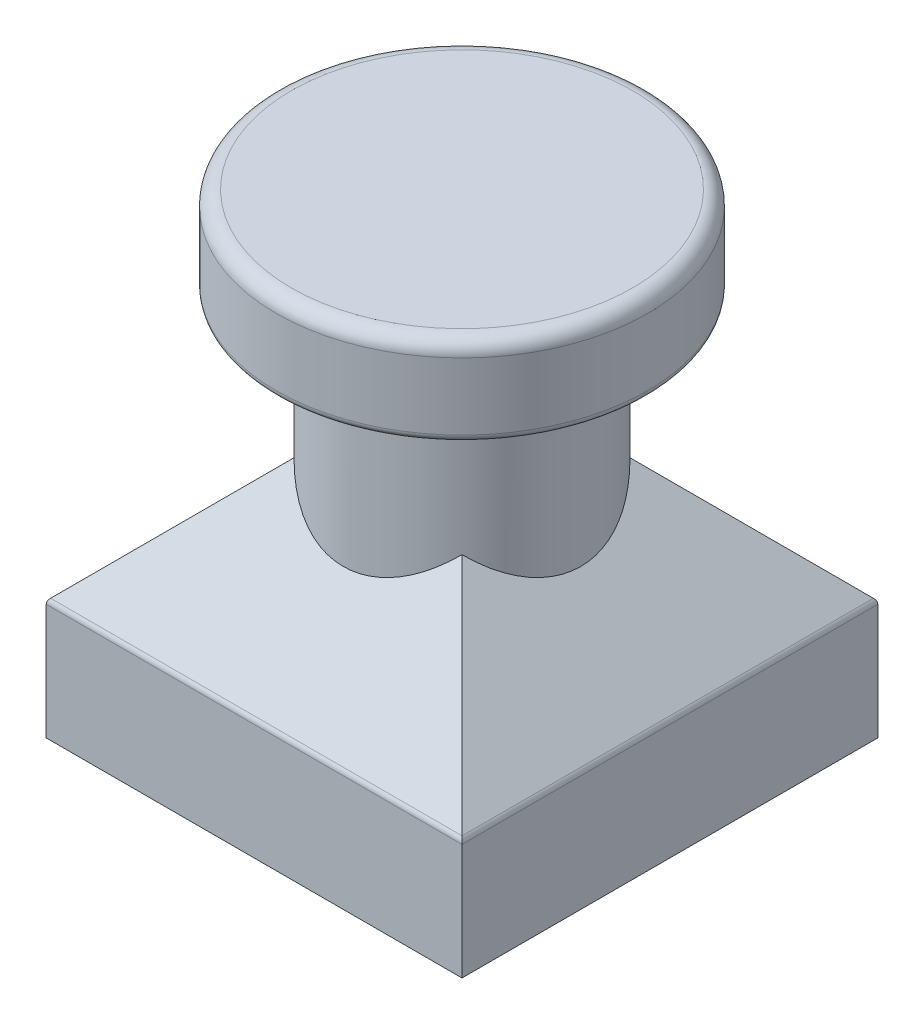
SolidWorks part; units mm, degrees
ref_plane "Ebene vorne" through (0, 0, 0) normal (0, 0, 1) x (1, 0, 0)
ref_plane "Ebene oben" through (0, 0, 0) normal (0, 1, 0) x (1, 0, 0)
ref_plane "Ebene rechts" through (0, 0, 0) normal (1, 0, 0) x (0, 0, -1)
sketch "Skizze1" plane through (0, 0, 0) normal (0, 1, 0) x (1, 0, 0)
  line L0 (-7, 0) -> (7, 0) construction
  line L1 (-7, 7) -> (7, 7)
  line L2 (-7, 7) -> (-7, -7)
  line L3 (-7, -7) -> (7, -7)
  line L4 (7, 7) -> (7, -7)
  line L5 (-7, 7) -> (7, -7) construction
  line L6 (-7, -7) -> (7, 7) construction
  line L7 (0, 7) -> (0, -7) construction
  point P0 (0, 0)
  dimension "D1" = 14
  dimension "D2" = 14
extrude "Aufsatz-Linear austragen1" add sketch "Skizze1" along normal blind 16
sketch "Skizze6" plane through (0, 0, 0) normal (1, 0, 0) x (0, 0, -1)
  line L0 (13.25, 16) -> (13.25, 9)
  line L2 (13.25, 9) -> (4, 9)
  line L3 (4, 9) -> (4, 13)
  line L4 (4, 13) -> (6.25, 13)
  line L5 (6.25, 13) -> (6.25, 16)
  line L6 (7, 16) -> (-7, 16) construction
  line L7 (6.25, 16) -> (13.25, 16)
  line L8 (0, 0) -> (0, 16)
  line L11 (0, 7.7) -> (0, -7.7) construction
  line L12 (0, 0) -> (0, 16) construction
  dimension "D1" = 4
  dimension "D2" = 3
  dimension "D3" = 4
  dimension "D4" = 2.25
revolve "Schnitt-Rotation4" cut sketch "Skizze6" angle 360 about L12 region at (0, 12.2672, -9.0323)
chamfer "Fase1" distance 5 angle 45 4 edges at (-7, 9, 0) (0, 9, -7) (7, 9, 0) (0, 9, 7)
fillet "Verrundung2" radius 0.5 1 edges at (0, 16, -6.25)
fillet "Verrundung3" radius 0.25 4 edges at (0, 4, -7) (7, 4, 0) (0, 4, 7) (-7, 4, 0)
fillet "Verrundung4" radius 0.25 1 edges at (0, 13, -6.25)
